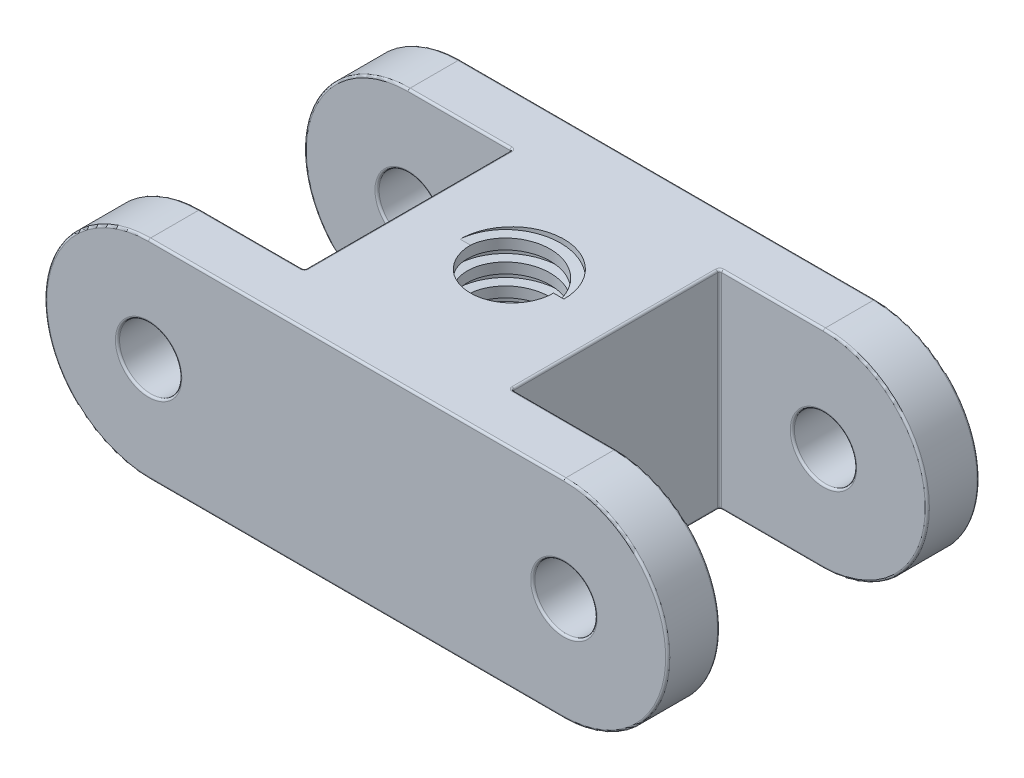
SolidWorks part; units mm, degrees
material "Nickel"
ref_plane "Front Plane" through (0, 0, 0) normal (0, 0, 1) x (1, 0, 0)
ref_plane "Top Plane" through (0, 0, 0) normal (0, 1, 0) x (1, 0, 0)
ref_plane "Right Plane" through (0, 0, 0) normal (1, 0, 0) x (0, 0, -1)
sketch "Sketch1" plane through (0, 0, 0) normal (0, 0, 1) x (1, 0, 0)
  line L1 (-20, 20) -> (20, 20)
  line L3 (-20, 0) -> (20, 0)
  arc A0 (-20, 20) -> (-20, 0) centre (-20, 10) ccw
  arc A1 (20, 0) -> (20, 20) centre (20, 10) ccw
  circle A2 centre (-20, 10) radius 3
  circle A3 centre (20, 10) radius 3
  point P4 (0, 0)
  dimension "D2" = 10
  dimension "D4" = 6
  dimension "D1" = 40
  dimension "D3" = 20
extrude "Boss-Extrude1" add sketch "Sketch1" along normal mid plane 30
sketch "Sketch2" plane through (0, 20, 0) normal (0, 1, 0) x (1, 0, 0)
  line L0 (0, 15) -> (0, 0) construction
  line L1 (20, 15) -> (-20, 15) construction
  line L2 (0, 0) -> (-35.8319, 0) construction
  line L3 (10, 0) -> (-10, 0) construction
  line L4 (-10, 10) -> (-60, 10)
  line L5 (-10, 10) -> (-10, -10)
  line L6 (-10, -10) -> (-60, -10)
  line L7 (-60, 10) -> (-60, -10)
  line L8 (60, 10) -> (60, -10)
  line L9 (10, -10) -> (60, -10)
  line L10 (10, 10) -> (10, -10)
  line L11 (10, 10) -> (60, 10)
  circle A0 centre (0, 0) radius 4
  dimension "D2" = 8
  dimension "D1" = 20
  dimension "D3" = 10
  dimension "D4" = 50
extrude "Cut-Extrude1" cut sketch "Sketch2" against normal through all both and the other way through all
sketch "Sketch3" plane through (0, 0, 0) normal (0, -1, 0) x (1, 0, 0)
  circle A0 centre (0, 0) radius 4 construction
  circle A1 centre (0, 0) radius 4
curve "Helix/Spiral1" pitch 2 height 30 radius 4 centre (0, 0, 0) axis (0, 1, 0) start towards (1, 0, 0)
sketch "Sketch5" plane through (0, 0, 0) normal (0, 0, 1) x (1, 0, 0)
  line L1 (4, 0) -> (5, 0)
  line L2 (4, 0) -> (4, -1)
  line L3 (4, -1) -> (5, -1)
  line L4 (5, 0) -> (5, -1)
  dimension "D1" = 1
  dimension "D2" = 1
sweep "Cut-Sweep1" cut profiles "Sketch5" path "Helix/Spiral1" align with end faces yes
fillet "Fillet1" radius 0.2 36 edges at (30, 10, 10) (15, 20, 10) (15, 0, 10) (23, 10, 10) (30, 10, -10) (15, 0, -10) (15, 20, -10) (17, 10, -10) (-30, 10, 10) (-15, 0, 10) (-15, 20, 10) (-17, 10, 10) (-30, 10, -10) (-15, 20, -10) (-15, 0, -10) (-23, 10, -10) (-10, 20, 0) (-10, 10, 10) (-10, 0, 0) (-10, 10, -10) (10, 20, 0) (10, 10, -10) (10, 0, 0) (10, 10, 10) (-17, 10, -15) (23, 10, -15) (0, 0, -15) (30, 10, -15) (0, 20, -15) (-30, 10, -15) (-17, 10, 15) (0, 20, 15) (30, 10, 15) (0, 0, 15) (-30, 10, 15) (23, 10, 15)
